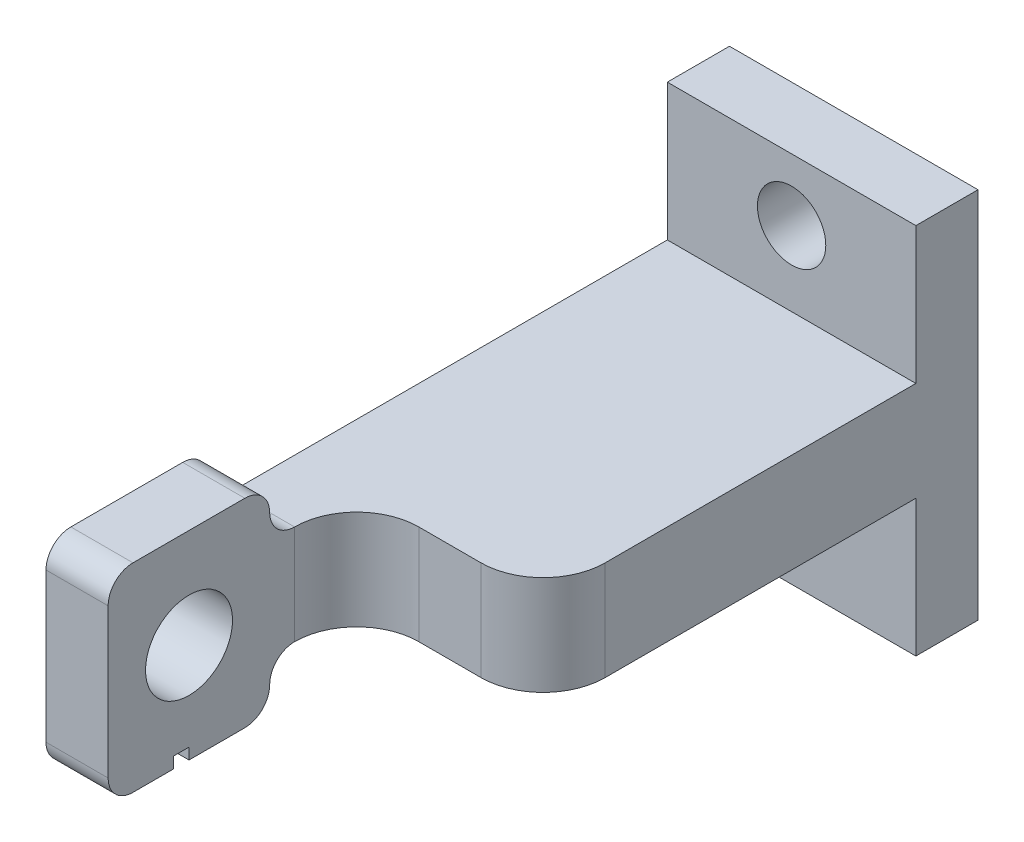
SolidWorks part; units mm, degrees
ref_plane "Front Plane" through (0, 0, 0) normal (0, 0, 1) x (1, 0, 0)
ref_plane "Top Plane" through (0, 0, 0) normal (0, 1, 0) x (1, 0, 0)
ref_plane "Right Plane" through (0, 0, 0) normal (1, 0, 0) x (0, 0, -1)
sketch "Sketch1" plane through (0, 0, 0) normal (0, 0, 1) x (1, 0, 0)
  line L0 (15, -17.7591) -> (15, -12.7591)
  line L1 (15, -12.7591) -> (25, -12.7591)
  line L2 (25, -37.5) -> (25, -8.6789) construction
  line L3 (25, -12.7591) -> (25, -42.7591)
  line L4 (25, -42.7591) -> (5, -42.7591)
  line L5 (5, -11.15) -> (5, -75) construction
  line L6 (5, -42.7591) -> (5, -12.7591)
  line L7 (5, -12.7591) -> (15, -12.7591)
  circle A0 centre (15, -17.7591) radius 2.75 construction
  circle A1 centre (15, -35.9197) radius 2.75 construction
  circle A2 centre (15, -35.9197) radius 2.75
  circle A3 centre (15, -17.7591) radius 2.75
  dimension "D1" = 5
  dimension "D2" = 30
extrude "Boss-Extrude1" add sketch "Sketch1" along normal blind 5 contours A3 L7 L6 L4 L3 L1 A2 region at (15, -27.8382, 0)
sketch "Sketch2" plane through (0, 0, 5) normal (0, 0, 1) x (1, 0, 0)
  line L0 (25, -27.7591) -> (5, -27.7591)
  line L1 (25, -12.7591) -> (25, -42.7591) construction
  line L2 (5, -42.7591) -> (5, -12.7591) construction
  line L3 (25, -23.7591) -> (5, -23.7591)
  line L4 (25, -31.7591) -> (5, -31.7591)
  line L5 (5, -23.7591) -> (5, -31.7591)
  line L6 (25, -31.7591) -> (25, -23.7591)
  line M1 (25, -42.7591) -> (25, -12.7591)
  line M3 (5, -12.7591) -> (5, -42.7591)
  dimension "D1" = 4
  dimension "D2" = 4
extrude "Boss-Extrude2" add sketch "Sketch2" along normal blind 50 contours L3 L0 M1 M3 | L4 L0 M1 M3 region at (15, -29.7591, 5) region at (15, -25.7591, 5)
sketch "Sketch3" plane through (25, 0, 0) normal (1, 0, 0) x (0, 0, -1)
  line L0 (-55, -27.7591) -> (-23.5332, -27.7591)
  line L1 (-55, -31.7591) -> (-55, -23.7591) construction
  line L2 (-38.3486, -22.7761) -> (-48.4906, -27.7591)
  arc A0 (11.052, 24.1625) -> (4.8993, 27.7147) centre (-7, 0) ccw construction
  circle A1 centre (-48.4906, -27.7591) radius 2
  dimension "D2" = 4
  dimension "D1" = 11.3
extrude "Cut-Extrude1" cut sketch "Sketch3" against normal through all both and the other way through all contours L2 A1 L0 | L0 A1 | L0 A1 L2 region at (25, -27.4599, 47.2031) region at (25, -28.608, 48.4906) region at (25, -26.8168, 48.7095)
sketch "Sketch5" plane through (0, 0, 55) normal (0, 0, 1) x (1, 0, 0)
  line L0 (25, -31.7591) -> (5, -31.7591) construction
  line L1 (25, -23.7591) -> (10, -23.7591)
  line L2 (25, -23.7591) -> (25, -31.7591)
  line L3 (25, -31.7591) -> (10, -31.7591)
  line L4 (10, -23.7591) -> (10, -31.7591)
  line L5 (10, -20.2591) -> (10, -35.2591) construction
extrude "Cut-Extrude2" cut sketch "Sketch5" against normal blind 15
sketch "Sketch6" plane through (0, 0, 40) normal (0, 0, 1) x (1, 0, 0)
  line L4 (25, -31.7591) -> (25, -23.7591)
  line L5 (25, -23.7591) -> (10, -23.7591)
  line L6 (10, -23.7591) -> (10, -31.7591)
  line L7 (10, -31.7591) -> (25, -31.7591)
  line L8 (25, -31.7591) -> (25, -23.7591)
  line L9 (25, -23.7591) -> (10, -23.7591)
  line L10 (10, -23.7591) -> (10, -31.7591)
  line L11 (10, -31.7591) -> (25, -31.7591)
  dimension "D1" = 0
extrude "Cut-Extrude3" cut sketch "Sketch6" against normal blind 5
fillet "Fillet1" radius 5 2 edges at (25, -27.7591, 35) (10, -27.7591, 35)
sketch "Sketch7" plane through (5, 0, 0) normal (-1, 0, 0) x (0, 0, 1)
  line L0 (55, -27.7591) -> (42, -27.7591)
  line L1 (55, -23.7591) -> (55, -31.7591) construction
  line L2 (55, -19.7591) -> (42, -19.7591)
  line L3 (55, -35.7591) -> (42, -35.7591)
  line L4 (55, -19.7591) -> (55, -35.7591)
  line L5 (42, -35.7591) -> (42, -19.7591)
  line M6 (5, -31.7591) -> (55, -31.7591)
  line M8 (55, -23.7591) -> (5, -23.7591)
  dimension "D1" = 13
  dimension "D2" = 8
  dimension "D3" = 8
extrude "Boss-Extrude3" add sketch "Sketch7" against normal blind 5 contours L5 L3 L4 M6 | L5 L4 L2 M8 region at (5, -21.7591, 48.5) region at (5, -33.7591, 48.5)
sketch "Sketch8" plane through (5, 0, 0) normal (-1, 0, 0) x (0, 0, 1)
  circle A0 centre (48.4906, -27.7591) radius 3.5
  dimension "D1" = 7
extrude "Cut-Extrude5" cut sketch "Sketch8" against normal through all
sketch "Sketch9" plane through (5, 0, 0) normal (-1, 0, 0) x (0, 0, 1)
  line L0 (48.4906, -24.2591) -> (48.4906, -36.2591) construction
  line L1 (48.4906, -36.2591) -> (48.4906, -34.8591)
  line L2 (49.7406, -36.2591) -> (49.7406, -34.8591)
  line L3 (47.2406, -36.2591) -> (47.2406, -34.8591)
  line L4 (49.7406, -36.2591) -> (47.2406, -36.2591)
  line L5 (47.2406, -34.8591) -> (49.7406, -34.8591)
  circle A0 centre (48.4906, -27.7591) radius 3.5 construction
  line M9 (42, -35.7591) -> (55, -35.7591)
  dimension "D1" = 12
  dimension "D2" = 1.4
  dimension "D3" = 1.25
  dimension "D4" = 1.25
extrude "Cut-Extrude6" cut sketch "Sketch9" against normal blind 5 contours L5 L1 L2 M9 | L4 L1 L3 M9 | L4 L2 L1 M9 region at (5, -36.0091, 47.8656) region at (5, -36.0091, 49.1156) region at (5, -35.3091, 49.1156)
fillet "Fillet2" radius 2 6 edges at (7.5, -23.7591, 42) (7.5, -31.7591, 42) (7.5, -35.7591, 42) (7.5, -19.7591, 42) (7.5, -19.7591, 55) (7.5, -35.7591, 55)
